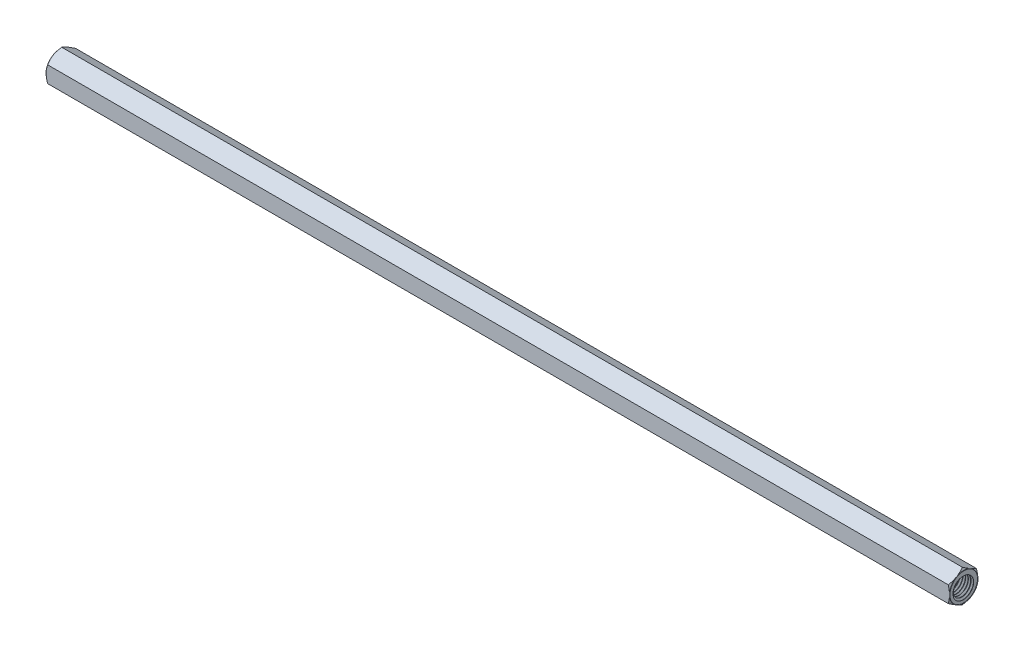
SolidWorks part; units mm, degrees
note: '?' marks a value the reader was unsure of.
material "6061-T6 (SS)"
ref_plane "Front Plane" through (0, 0, 0) normal (0, 0, 1) x (1, 0, 0)
ref_plane "Top Plane" through (0, 0, 0) normal (0, 1, 0) x (1, 0, 0)
ref_plane "Right Plane" through (0, 0, 0) normal (1, 0, 0) x (0, 0, -1)
sketch "Sketch1" plane through (0, 0, 0) normal (0, 0, 1) x (1, 0, 0)
  line L0 (-152.4, 0) -> (152.4, 0) construction
  line L1 (-152.4, 3.175) -> (-152.4, -3.175) construction
  line L2 (152.4, 3.175) -> (152.4, -3.175) construction
  line L3 (0, 4.7625) -> (0, -4.7625) construction
  line L4 (133.35, 3.175) -> (133.35, -3.175) construction
  line L5 (-133.35, 3.175) -> (-133.35, -3.175) construction
  line L6 (-152.4, 3.175) -> (-133.35, 3.175) construction
  line L7 (-152.4, -3.175) -> (-133.35, -3.175) construction
  line L8 (133.35, -3.175) -> (152.4, -3.175) construction
  line L9 (133.35, 3.175) -> (152.4, 3.175) construction
  point P7 (-133.35, 0)
  point P8 (133.35, 0)
  point P17 (145.1429, -3.175)
  dimension "Length" = 304.8
  dimension "D1" = 19.05
  dimension "Thread Size" = 6.35
  dimension "Rod OD" = 9.525
  dimension "Thread Length" = 19.05
  dimension "D2" = 266.7
  dimension "D5" = 7.2571
sketch "Sketch2" plane through (0, 0, 0) normal (1, 0, 0) x (0, 0, -1)
  line L1 (4.7625, 2.7496) -> (0, 5.4993)
  line L2 (0, 5.4993) -> (-4.7625, 2.7496)
  line L3 (-4.7625, 2.7496) -> (-4.7625, -2.7496)
  line L4 (-4.7625, -2.7496) -> (0, -5.4993)
  line L5 (0, -5.4993) -> (4.7625, -2.7496)
  line L6 (4.7625, -2.7496) -> (4.7625, 2.7496)
  circle A1 centre (0, 0) radius 4.7625 construction
  point P12 (0, 4.7625)
extrude "Boss-Extrude1" add sketch "Sketch2" against normal up to vertex (152.4 mm away) and the other way up to vertex (152.4 mm away) up to point (-152.4, 0, 0) other way up to point (152.4, 0, 0)
sketch "Sketch4" plane through (-152.4, 0, 0) normal (-1, 0, 0) x (0, 0, 1)
  circle A0 centre (0, 0) radius 3.175
extrude "Cut-Extrude1" cut sketch "Sketch4" against normal up to vertex (19.05 mm away) up to point (-133.35, 0, 0)
sketch "Sketch7" plane through (-133.35, 0, 0) normal (-1, 0, 0) x (0, 0, 1)
  circle A1 centre (0, 0) radius 3.175
  circle A2 centre (0, 0) radius 3.175
  dimension "D1" = 0
extrude "Cut-Extrude2" cut sketch "Sketch7" against normal through all draft 59
sketch "Sketch5" plane through (-152.4, 0, 0) normal (-1, 0, 0) x (0, 0, 1)
  line L0 (0, 5.4993) -> (4.7625, 2.7496) construction
  circle A0 centre (0, 0) radius 4.7625
extrude "Cut-Extrude-Thin2" cut sketch "Sketch5" against normal through all draft 60 thin
mirror "Mirror1" about plane through (0, 0, 0) normal (1, 0, 0) of "Cut-Extrude1", "Cut-Extrude-Thin2", "Cut-Extrude2"
sketch "Sketch3" plane through (-152.4, 0, 0) normal (1, 0, 0) x (0, 0, -1)
  circle A0 centre (0, 0) radius 3.175 construction
  circle A1 centre (0, 0) radius 3.175
ref_axis "Center Axis 1" through (-252.2905, 0, 0) along (1, 0, 0)?
ref_plane "Contact Plane 1" through (-152.4, 0, 0) normal (-1, 0, 0) x (0, 0, 1)
ref_plane "Contact Plane 2" through (152.4, 0, 0) normal (1, 0, 0) x (0, 0, -1)
curve "Helix/Spiral1" pitch 0.9071 height 19.05 turns 21 parameters "pitch"=0.9071
sketch "Sketch6" plane through (0, 0, 0) normal (0, 0, 1) x (1, 0, 0)
  line L0 (-153.2504, 3.0768) -> (-152.3433, 3.0768) construction
  line L1 (-152.3433, 3.0768) -> (-152.7969, 3.8624) construction
  line L2 (-152.7969, 3.8624) -> (-153.2504, 3.0768) construction
  line L3 (-153.1937, 3.175) -> (-152.4, 3.175) construction
  line L4 (-152.7969, 3.0768) -> (-152.7969, 3.175) construction
  line L5 (-153.2221, 3.1259) -> (-152.3717, 3.1259) construction
  line L6 (-152.8536, 3.7642) -> (-152.7402, 3.7642) construction
  line L7 (-152.7969, 3.7642) -> (-152.7969, 3.8624) construction
  line L8 (-152.8536, 3.7642) -> (-152.7402, 3.7642) construction
  line L10 (-152.8536, 3.7642) -> (-153.2221, 3.1259)
  line L11 (-153.2221, 3.1259) -> (-152.3717, 3.1259)
  line L12 (-152.3717, 3.1259) -> (-152.7402, 3.7642)
  line L13 (-152.8536, 3.7642) -> (-152.7402, 3.7642)
  point P10 (-152.7969, 3.1259)
  dimension "D1" = 0.9071
  dimension "D2" = 0.1134
sweep "Cut-Sweep1" cut profiles "Sketch6" path "Helix/Spiral1"
mirror "Mirror2" about plane through (0, 0, 0) normal (1, 0, 0) of "Cut-Sweep1"
sketch "Sketch8" plane through (152.4, 0, 0) normal (1, 0, 0) x (0, 0, -1)
  circle A1 centre (0, 0) radius 4.75
  dimension "D1" = 9.5
extrude "Boss-Extrude2" add sketch "Sketch8" along normal blind 0.1
sketch "Sketch9" plane through (152.5, 0, 0) normal (1, 0, 0) x (0, 0, -1)
  circle A0 centre (0, 0) radius 4.7
  dimension "D1" = 9.4
extrude "Cut-Extrude3" cut sketch "Sketch9" against normal blind 0.1
sketch "Sketch10" plane through (-152.4, 0, 0) normal (-1, 0, 0) x (0, 0, 1)
  circle A0 centre (0, 0) radius 4.75
  dimension "D1" = 9.5
extrude "Boss-Extrude3" add sketch "Sketch10" along normal blind 0.1
sketch "Sketch11" plane through (-152.5, 0, 0) normal (-1, 0, 0) x (0, 0, 1)
  circle A0 centre (0, 0) radius 4.7
  dimension "D1" = 9.4
extrude "Cut-Extrude4" cut sketch "Sketch11" against normal blind 0.1
equation "\"D1@Sketch1\" = \"Thread Length@Sketch1\""
equation "\"D3@Helix/Spiral1\"=\"Thread Length@Sketch1\""
equation "\"D5@Sketch1\" = \"pitch@Helix/Spiral1\"*8"
equation "\"D1@Sketch6\"=\"pitch@Helix/Spiral1\""
equation "\"D2@Sketch6\"=\"D1@Sketch6\"/ 1/8"
